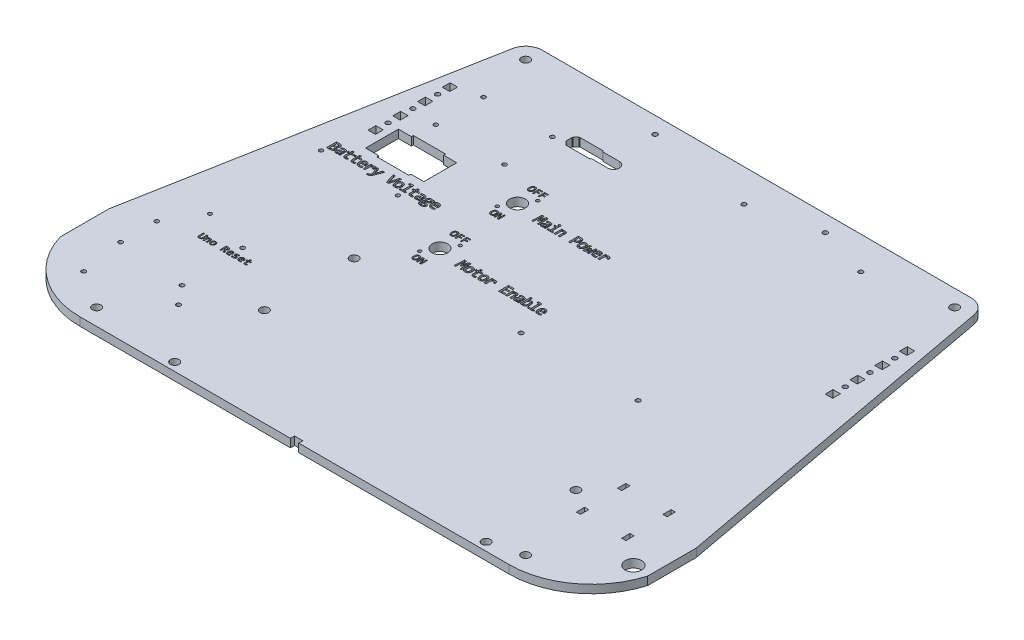
SolidWorks part; units mm, degrees
material "Acrylic (Medium-high impact)"
ref_plane "Front Plane" through (0, 0, 0) normal (0, 0, 1) x (1, 0, 0)
ref_plane "Top Plane" through (0, 0, 0) normal (0, 1, 0) x (1, 0, 0)
ref_plane "Right Plane" through (0, 0, 0) normal (1, 0, 0) x (0, 0, -1)
sketch "Sketch1" plane through (0, 0, 0) normal (0, 1, 0) x (1, 0, 0)
  line L0 (-165.1, -177.8) -> (-3.175, -177.8)
  line L1 (165.1, -165.1) -> (-165.1, -165.1) construction
  line L2 (165.1, -165.1) -> (165.1, 165.1) construction
  line L3 (165.1, 165.1) -> (-165.1, 165.1) construction
  line L4 (-165.1, -165.1) -> (-165.1, 165.1) construction
  line L5 (165.1, -165.1) -> (-165.1, 165.1) construction
  line L6 (165.1, 165.1) -> (-165.1, -165.1) construction
  line L7 (-165.1, 177.8) -> (165.1, 177.8)
  line L8 (-226.06, -94.7416) -> (-177.5883, 167.4091)
  line L9 (177.5883, 167.4091) -> (226.06, -94.7416)
  line L10 (0, 0) -> (0, 177.8) construction
  line L11 (0, 0) -> (0, -177.8) construction
  line L12 (-65.5, 165.1) -> (65.5, 165.1) construction
  line L13 (-3.175, -177.8) -> (-3.175, -174.625)
  line L14 (-3.175, -174.625) -> (3.175, -174.625)
  line L15 (3.175, -174.625) -> (3.175, -177.8)
  line L16 (3.175, -177.8) -> (165.1, -177.8)
  line L17 (-178.77, 101.6) -> (-178.77, 114.65) construction
  line L18 (-178.77, 82.55) -> (-178.77, 95.6) construction
  line L19 (-178.77, 63.5) -> (-178.77, 76.55) construction
  line L20 (-173.07, 63.5) -> (-178.77, 63.5)
  line L21 (-173.07, 57.5) -> (-173.07, 63.5)
  line L22 (-178.77, 57.5) -> (-173.07, 57.5)
  line L23 (-178.77, 63.5) -> (-178.77, 57.5)
  line L24 (-173.07, 82.55) -> (-178.77, 82.55)
  line L25 (-173.07, 76.55) -> (-173.07, 82.55)
  line L26 (-178.77, 76.55) -> (-173.07, 76.55)
  line L27 (-178.77, 82.55) -> (-178.77, 76.55)
  line L28 (-173.07, 101.6) -> (-178.77, 101.6)
  line L29 (-173.07, 95.6) -> (-173.07, 101.6)
  line L30 (-178.77, 95.6) -> (-173.07, 95.6)
  line L31 (-178.77, 101.6) -> (-178.77, 95.6)
  line L32 (-173.07, 120.65) -> (-178.77, 120.65)
  line L33 (178.77, 120.65) -> (178.77, 114.65)
  line L34 (178.77, 114.65) -> (173.07, 114.65)
  line L35 (173.07, 114.65) -> (173.07, 120.65)
  line L36 (173.07, 120.65) -> (178.77, 120.65)
  line L37 (178.77, 101.6) -> (178.77, 95.6)
  line L38 (178.77, 95.6) -> (173.07, 95.6)
  line L39 (173.07, 95.6) -> (173.07, 101.6)
  line L40 (173.07, 101.6) -> (178.77, 101.6)
  line L41 (178.77, 82.55) -> (178.77, 76.55)
  line L42 (178.77, 76.55) -> (173.07, 76.55)
  line L43 (173.07, 76.55) -> (173.07, 82.55)
  line L44 (173.07, 82.55) -> (178.77, 82.55)
  line L45 (178.77, 63.5) -> (178.77, 57.5)
  line L46 (178.77, 57.5) -> (173.07, 57.5)
  line L47 (173.07, 57.5) -> (173.07, 63.5)
  line L48 (173.07, 63.5) -> (178.77, 63.5)
  line L49 (178.77, 63.5) -> (178.77, 76.55) construction
  line L50 (178.77, 82.55) -> (178.77, 95.6) construction
  line L51 (178.77, 101.6) -> (178.77, 114.65) construction
  line L52 (-173.07, 114.65) -> (-173.07, 120.65)
  line L53 (-178.77, 114.65) -> (-173.07, 114.65)
  line L54 (-178.77, 120.65) -> (-178.77, 114.65)
  line L55 (-178.77, 114.65) -> (-173.07, 101.6) construction
  line L56 (-173.07, 95.6) -> (-178.77, 82.55) construction
  line L57 (-178.77, 76.55) -> (-173.07, 63.5) construction
  line L58 (173.07, 114.65) -> (178.77, 101.6) construction
  line L59 (178.77, 95.6) -> (173.07, 82.55) construction
  line L60 (173.07, 76.55) -> (178.77, 63.5) construction
  line L61 (-226.06, -94.7416) -> (-226.06, -132.08)
  line L63 (226.06, -132.08) -> (226.06, -94.7416)
  circle A0 centre (-165.1, 165.1) radius 3.2639
  circle A1 centre (165.1, 165.1) radius 3.2639
  circle A2 centre (165.1, -165.1) radius 3.2639
  circle A3 centre (-165.1, -165.1) radius 3.2639
  arc A4 (-165.1, 177.8) -> (-177.5883, 167.4091) centre (-165.1, 165.1) ccw
  arc A5 (165.1, 177.8) -> (177.5883, 167.4091) centre (165.1, 165.1) cw
  arc A6 (-226.06, -132.08) -> (-165.1, -177.8) centre (-165.1, -114.3) ccw
  arc A7 (165.1, -177.8) -> (226.06, -132.08) centre (165.1, -114.3) ccw
  circle A8 centre (-65.5, 165.1) radius 1.8288
  circle A9 centre (65.5, 165.1) radius 1.8288
  circle A10 centre (-175.92, 70.025) radius 1.778
  circle A11 centre (-175.92, 89.075) radius 1.778
  circle A12 centre (-175.92, 108.125) radius 1.778
  circle A13 centre (175.92, 70.025) radius 1.778
  circle A14 centre (175.92, 89.075) radius 1.778
  circle A15 centre (175.92, 108.125) radius 1.778
  point P0 (0, 0)
  point P1 (165.1, -114.3)
  point P27 (0, 165.1)
  point P32 (0, -174.625)
  dimension "D2" = 6.5278
  dimension "D6" = 3.6576
  dimension "D16" = 3.556
  dimension "D1" = 330.2
  dimension "D3" = 12.7
  dimension "D4" = 12.7
  dimension "D5" = 63.5
  dimension "D7" = 131
  dimension "D8" = 165.1
  dimension "D9" = 3.175
  dimension "D10" = 6.35
  dimension "D11" = 5.7
  dimension "D12" = 6
  dimension "D13" = 13.05
  dimension "D14" = 57.15
  dimension "D15" = 7.97
  dimension "D17" = 452.12
extrude "Boss-Extrude1" add sketch "Sketch1" along normal blind 6.35
sketch "Sketch2" plane through (0, 6.35, 0) normal (0, 1, 0) x (1, 0, 0)
  line L0 (-95.3811, 131.405) -> (-92.6311, 134.155)
  line L2 (-95.3811, 134.155) -> (-73.8811, 134.155)
  line L3 (-95.3811, 134.155) -> (-95.3811, 123.655)
  line L4 (-73.8811, 133.35) -> (-61.1811, 133.35)
  line L5 (-61.1811, 124.46) -> (-73.8811, 124.46)
  line L6 (165.1, 177.8) -> (-165.1, 177.8) construction
  line L7 (-95.3811, 123.655) -> (-73.8811, 123.655)
  line L8 (-73.8811, 134.155) -> (-73.8811, 123.655)
  line L9 (-92.6311, 123.655) -> (-95.3811, 126.405)
  line L10 (-61.1811, 128.905) -> (-95.3811, 128.905) construction
  arc A2 (-61.1811, 133.35) -> (-61.1811, 124.46) centre (-61.1811, 128.905) cw
  dimension "D1" = 8.89
  dimension "D2" = 12.7
  dimension "D3" = 44.45
  dimension "D4" = 61.1811
  dimension "D5" = 21.5
  dimension "D6" = 10.5
  dimension "D7" = 45
  dimension "D8" = 45
  dimension "D9" = 5
extrude "Cut-Extrude1" cut sketch "Sketch2" against normal through all contours A2 L4 L8 L5 | L10 L8 L2 L0 L3 | L8 L10 L3 L9 L7 region at (-84.2903, 6.35, -131.4708) region at (-84.2903, 6.35, -126.3392) region at (-73.688, 6.35, -131.1275)
sketch "Sketch3" plane through (0, 6.35, -6.35) normal (0, -1, 0) x (1, 0, 0)
  line L0 (165.1, -171.45) -> (-165.1, -171.45) construction
  line L1 (105.325, -146.2786) -> (105.325, 25.1714) construction
  line L2 (105.325, -146.2786) -> (15.325, -146.2786) construction
  line L3 (15.325, -146.2786) -> (15.325, 25.1714) construction
  line L4 (105.325, 25.1714) -> (15.325, 25.1714) construction
  line L5 (105.325, -146.2786) -> (15.325, 25.1714) construction
  line L6 (15.325, -146.2786) -> (105.325, 25.1714) construction
  circle A0 centre (15.325, -146.2786) radius 1.7
  circle A1 centre (15.325, 25.1714) radius 1.7
  circle A2 centre (105.325, 25.1714) radius 1.7
  circle A3 centre (105.325, -146.2786) radius 1.7
  point P0 (60.325, -60.5536)
  dimension "D1" = 3.4
  dimension "D2" = 90
  dimension "D3" = 171.45
  dimension "D4" = 110.8964
  dimension "D5" = 104.775
extrude "Cut-Extrude6" cut sketch "Sketch3" along normal through all
sketch "Sketch4" plane through (0, 6.35, 0) normal (0, 1, 0) x (1, 0, 0)
  line L0 (165.1, 177.8) -> (-165.1, 177.8) construction
  line L1 (-167.7882, 69.85) -> (-157.8147, 69.85)
  line L2 (-167.7882, 69.85) -> (-167.7882, 44.6198)
  line L3 (-167.7882, 44.6198) -> (-157.8147, 44.6198)
  line L4 (-122.9492, 69.85) -> (-122.9492, 44.6198)
  line L5 (-145.3687, 71.374) -> (-145.3687, 57.2349) construction
  line L6 (-132.9227, 44.6198) -> (-122.9492, 44.6198)
  line L7 (-157.8147, 69.85) -> (-157.8147, 71.374)
  line L8 (-157.8147, 71.374) -> (-132.9227, 71.374)
  line L9 (-132.9227, 69.85) -> (-132.9227, 71.374)
  line L10 (-167.7882, 57.2349) -> (-122.9492, 57.2349) construction
  line L11 (-132.9227, 44.6198) -> (-132.9227, 43.0958)
  line L12 (-157.8147, 43.0958) -> (-132.9227, 43.0958)
  line L13 (-157.8147, 44.6198) -> (-157.8147, 43.0958)
  line L14 (-132.9227, 69.85) -> (-122.9492, 69.85)
  line L15 (-78.2796, 56.4026) -> (-66.3965, 75.7796) construction
  line L16 (-78.2796, -3.3289) -> (-66.3965, 16.0482) construction
  line L17 (-72.338, 91.3891) -> (-72.338, 44.1198) construction
  line L18 (-72.338, 29.0763) -> (-72.338, -7.422) construction
  circle A0 centre (-72.338, 66.0911) radius 6
  circle A1 centre (-72.338, 6.3597) radius 6
  circle A2 centre (-66.3965, 75.7796) radius 1.25
  circle A3 centre (-78.2796, 56.4026) radius 1.25
  circle A4 centre (-66.3965, 16.0482) radius 1.25
  circle A5 centre (-78.2796, -3.3289) radius 1.25
  dimension "D1" = 12
  dimension "D10" = 2.5
  dimension "D2" = 44.839
  dimension "D3" = 25.2302
  dimension "D4" = 72.338
  dimension "D5" = 6.3597
  dimension "D6" = 66.0911
  dimension "D7" = 72.338
  dimension "D8" = 107.95
  dimension "D9" = 122.9492
  dimension "D11" = 22.7305
  dimension "D12" = 31.519
  dimension "D13" = 31.519
  dimension "D14" = 22.7305
  dimension "D19" = 24.892
  dimension "D20" = 1.524
extrude "Cut-Extrude7" cut sketch "Sketch4" against normal through all
sketch "Sketch5" plane through (0, 6.35, 0) normal (0, 1, 0) x (1, 0, 0)
  line L0 (-72.338, 60.0911) -> (16.4248, 60.0911) construction
  line L1 (-72.338, 0.3597) -> (21.2307, 0.3597) construction
  line L2 (-183.8192, 29.9147) -> (-66.0177, 29.9147) construction
  line L4 (-78.688, 78.7911) -> (-59.7976, 78.7911) construction
  line L5 (-77.418, 48.3111) -> (-57.2576, 48.3111) construction
  line L6 (-78.688, 19.0597) -> (-61.9228, 19.0597) construction
  line L7 (-77.418, -11.4203) -> (-57.2576, -11.4203) construction
  circle A0 centre (-72.338, 66.0911) radius 6 construction
  circle A1 centre (-72.338, 6.3597) radius 6 construction
  text T0 "   Main Power" font "Consolas" height 7.62
  text T1 "   Motor Enable" font "Consolas" height 7.62
  text T2 "Battery Voltage" font "Consolas" height 7.62
  text T3 "OFF" font "Consolas" height 5.08
  text T4 "OFF\r\n" font "Consolas" height 5.08
  text T5 "ON" font "Consolas" height 5.08
  text T6 "ON" font "Consolas" height 5.08
  dimension "D2" = 6.35
  dimension "D3" = 12.7
  dimension "D4" = 12.7
  dimension "D5" = 6.35
  dimension "D6" = 5.08
  dimension "D7" = 17.78
  dimension "D8" = 5.08
  dimension "D9" = 17.78
extrude "Cut-Extrude8" cut sketch "Sketch5" against normal blind 1.5875
sketch "Sketch6" plane through (0, 6.35, 0) normal (0, 1, 0) x (1, 0, 0)
  line L0 (159.094, -113.7425) -> (190.844, -113.7425) construction
  line L1 (187.9752, -69.2925) -> (161.9752, -69.2925) construction
  line L2 (187.9752, -142.2925) -> (187.9752, -69.2925) construction
  line L3 (165.9752, -146.2925) -> (183.9752, -146.2925) construction
  line L4 (159.094, -81.9925) -> (190.844, -81.9925) construction
  line L5 (190.844, -78.8175) -> (194.019, -78.8175)
  line L6 (190.844, -78.8175) -> (190.844, -85.1675)
  line L7 (190.844, -85.1675) -> (194.019, -85.1675)
  line L8 (194.019, -78.8175) -> (194.019, -85.1675)
  line L9 (155.919, -78.8175) -> (159.094, -78.8175)
  line L10 (155.919, -78.8175) -> (155.919, -85.1675)
  line L11 (155.919, -85.1675) -> (159.094, -85.1675)
  line L12 (159.094, -78.8175) -> (159.094, -85.1675)
  line L13 (155.919, -110.5675) -> (159.094, -110.5675)
  line L14 (155.919, -110.5675) -> (155.919, -116.9175)
  line L15 (155.919, -116.9175) -> (159.094, -116.9175)
  line L16 (159.094, -110.5675) -> (159.094, -116.9175)
  line L17 (190.844, -110.5675) -> (194.019, -110.5675)
  line L18 (190.844, -110.5675) -> (190.844, -116.9175)
  line L19 (190.844, -116.9175) -> (194.019, -116.9175)
  line L20 (194.019, -110.5675) -> (194.019, -116.9175)
  line L21 (174.9667, -57.7925) -> (174.9752, -146.2925) construction
  line L22 (169.1667, -57.7925) -> (180.7667, -57.7925) construction
  circle A0 centre (-156.3306, 123.8842) radius 1.5875
  circle A1 centre (-103.3306, 123.8842) radius 1.5875
  circle A2 centre (-103.3306, 87.0842) radius 1.5875
  circle A3 centre (-156.3306, 87.0842) radius 1.5875
  circle A4 centre (-183.8098, -59.1367) radius 1.4732
  circle A5 centre (-183.3027, 25.8618) radius 1.4732
  circle A6 centre (-123.8037, 25.5068) radius 1.4793
  circle A7 centre (-199.3418, -84.5435) radius 1.6
  circle A8 centre (-199.3418, -112.4435) radius 1.6
  circle A9 centre (-146.9418, -117.5435) radius 1.6
  circle A10 centre (-148.5418, -69.2435) radius 1.6
  circle A11 centre (-194.0161, -146.1037) radius 1.651
  circle A12 centre (-135.2786, -131.8162) radius 1.651
  circle A13 centre (-98.6512, -33.3375) radius 3.2639
  circle A14 centre (-98.6512, -102.3938) radius 3.2639
  circle A15 centre (-98.6512, -171.45) radius 3.2639
  circle A16 centre (141.0613, -171.45) radius 3.2639
  circle A17 centre (141.0613, -102.3938) radius 3.2639
  circle A18 centre (213.3752, -130.4429) radius 6.35
  circle A20 centre (-156.3306, 123.8842) radius 1.5875 construction
  circle A21 centre (-156.3306, 87.0842) radius 1.5875 construction
  circle A22 centre (-103.3306, 123.8842) radius 1.5875 construction
  point P78 (174.969, -81.9925)
  point P83 (174.969, -113.7425)
  dimension "D1" = 12.7
  dimension "D9" = 6.5278
  dimension "D2" = 25.4
  dimension "D3" = 15.8496
  dimension "D4" = 6.35
  dimension "D5" = 3.175
  dimension "D6" = 31.75
  dimension "D7" = 31.75
  dimension "D8" = 12.7
extrude "Cut-Extrude9" cut sketch "Sketch6" against normal through all
fillet "Fillet1" radius 1 6 edges at (-73.8811, 3.175, -134.155) (-73.8811, 3.175, -123.655) (-92.6311, 3.175, -123.655) (-92.6311, 3.175, -134.155) (-95.3811, 3.175, -126.405) (-95.3811, 3.175, -131.405)
sketch "Sketch7" plane through (0, 6.35, 0) normal (0, 1, 0) x (1, 0, 0)
  line L0 (-173.9418, -79.4035) -> (-133.8969, -79.4035) construction
  circle A0 centre (-148.5418, -69.2435) radius 1.6 construction
  text T0 "Uno Reset" font "Consolas" height 5.08
  dimension "D1" = 25.4
  dimension "D2" = 10.16
extrude "Cut-Extrude10" cut sketch "Sketch7" against normal blind 1.5875
sketch "Sketch8" plane through (0, 6.35, 0) normal (0, 1, 0) x (1, 0, 0)
  line L0 (172.9512, 556.6121) -> (11.0262, 556.6121) construction
  line L1 (-231.45, 624.0398) -> (225.75, 624.0398) construction
  line L2 (-231.45, 624.0398) -> (-231.45, -188.7602) construction
  line L3 (-231.45, -188.7602) -> (225.75, -188.7602) construction
  line L4 (225.75, 624.0398) -> (225.75, -188.7602) construction
  line L5 (11.0262, 556.6121) -> (11.0262, 553.4371) construction
  line L6 (11.0262, 553.4371) -> (4.6762, 553.4371) construction
  line L7 (4.6762, 553.4371) -> (4.6762, 556.6121) construction
  line L8 (4.6762, 556.6121) -> (-157.2488, 556.6121) construction
  line L9 (-219.6904, 481.5667) -> (-169.7371, 211.403) construction
  line L10 (-157.2488, 201.0121) -> (172.9512, 201.0121) construction
  line L11 (185.4396, 211.403) -> (235.3928, 481.5667) construction
  line L12 (-165.1, -177.8) -> (-3.175, -177.8)
  line L13 (-3.175, -177.8) -> (-3.175, -174.625)
  line L14 (-3.175, -174.625) -> (3.175, -174.625)
  line L15 (3.175, -174.625) -> (3.175, -177.8)
  line L16 (3.175, -177.8) -> (165.1, -177.8)
  line L17 (226.06, -94.7416) -> (177.5883, 167.4091)
  line L18 (165.1, 177.8) -> (-165.1, 177.8)
  line L19 (-177.5883, 167.4091) -> (-226.06, -94.7416)
  line L20 (-165.1, -177.8) -> (-3.175, -177.8)
  line L21 (-3.175, -177.8) -> (-3.175, -174.625)
  line L22 (-3.175, -174.625) -> (3.175, -174.625)
  line L23 (3.175, -174.625) -> (3.175, -177.8)
  line L24 (3.175, -177.8) -> (165.1, -177.8)
  line L25 (226.06, -94.7416) -> (177.5883, 167.4091)
  line L26 (165.1, 177.8) -> (-165.1, 177.8)
  line L27 (-177.5883, 167.4091) -> (-226.06, -94.7416)
  line L28 (-157.2488, 556.6121) -> (-157.2488, 493.1121) construction
  line L29 (-157.2488, 493.1121) -> (-219.6904, 481.5667) construction
  line L30 (235.3928, 481.5667) -> (172.9512, 493.1121) construction
  line L31 (172.9512, 493.1121) -> (172.9512, 556.6121) construction
  line L32 (185.4396, 211.403) -> (172.9512, 213.7121) construction
  line L33 (172.9512, 213.7121) -> (172.9512, 201.0121) construction
  line L34 (-157.2488, 201.0121) -> (-157.2488, 213.7121) construction
  line L35 (-157.2488, 213.7121) -> (-169.7371, 211.403) construction
  line L46 (226.06, -132.08) -> (226.06, -94.7416)
  line L47 (226.06, -132.08) -> (226.06, -94.7416)
  line L48 (-226.06, -94.7416) -> (-226.06, -132.08)
  line L49 (-226.06, -94.7416) -> (-226.06, -132.08)
  arc A0 (235.3928, 481.5667) -> (172.9512, 556.6121) centre (172.9512, 493.1121) ccw construction
  arc A1 (-157.2488, 556.6121) -> (-219.6904, 481.5667) centre (-157.2488, 493.1121) ccw construction
  arc A2 (-169.7371, 211.403) -> (-157.2488, 201.0121) centre (-157.2488, 213.7121) ccw construction
  arc A3 (172.9512, 201.0121) -> (185.4396, 211.403) centre (172.9512, 213.7121) ccw construction
  arc A4 (-226.06, -132.08) -> (-165.1, -177.8) centre (-165.1, -114.3) ccw
  arc A5 (165.1, -177.8) -> (226.06, -132.08) centre (165.1, -114.3) ccw
  arc A6 (177.5883, 167.4091) -> (165.1, 177.8) centre (165.1, 165.1) ccw
  arc A7 (-165.1, 177.8) -> (-177.5883, 167.4091) centre (-165.1, 165.1) ccw
  arc A8 (-226.06, -132.08) -> (-165.1, -177.8) centre (-165.1, -114.3) ccw
  arc A9 (165.1, -177.8) -> (226.06, -132.08) centre (165.1, -114.3) ccw
  arc A10 (177.5883, 167.4091) -> (165.1, 177.8) centre (165.1, 165.1) ccw
  arc A11 (-165.1, 177.8) -> (-177.5883, 167.4091) centre (-165.1, 165.1) ccw
  dimension "D4" = 63.5
  dimension "D5" = 12.7
  dimension "D14" = 259.524
  dimension "D1" = 812.8
  dimension "D2" = 457.2
  dimension "D6" = 161.925
  dimension "D7" = 274.743
  dimension "D8" = 330.2
  dimension "D9" = 6.35
  dimension "D10" = 3.175
  dimension "D11" = 79.524
  dimension "D12" = 100.476
  dimension "D13" = 100.476
  dimension "D15" = 259.524
  dimension "D16" = 79.524
  dimension "D17" = 79.524
  dimension "D3" = 0
